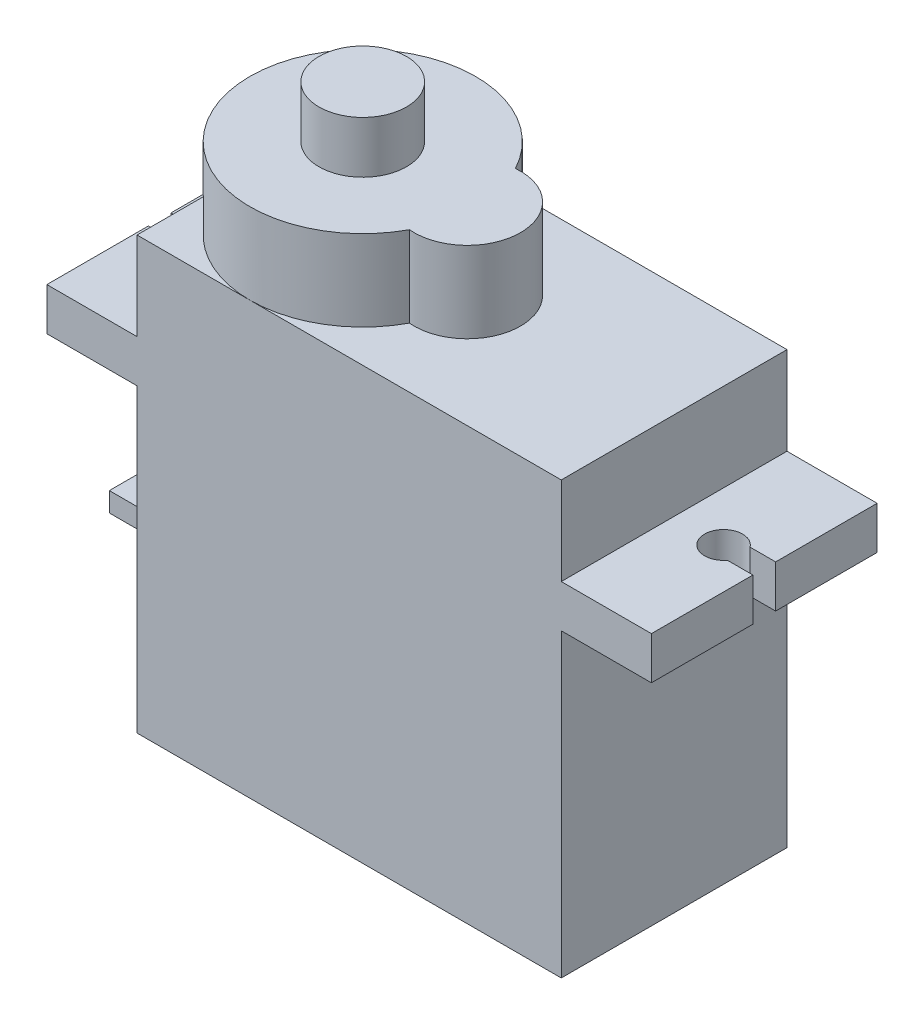
SolidWorks part; units mm, degrees
ref_plane "Front Plane" through (0, 0, 0) normal (0, 0, 1) x (1, 0, 0)
ref_plane "Top Plane" through (0, 0, 0) normal (0, 1, 0) x (1, 0, 0)
ref_plane "Right Plane" through (0, 0, 0) normal (1, 0, 0) x (0, 0, -1)
sketch "Sketch1" plane through (0, 0, 0) normal (0, 1, 0) x (1, 0, 0)
  line L1 (0, 0) -> (22.7711, 0)
  line L2 (0, 0) -> (0, 12.1158)
  line L3 (0, 12.1158) -> (22.7711, 12.1158)
  line L4 (22.7711, 0) -> (22.7711, 12.1158)
  dimension "D1" = 12.1158
  dimension "D2" = 22.7711
extrude "Boss-Extrude1" add sketch "Sketch1" along normal blind 23.1521
ref_plane "Plane1" through (0, 18.4277, 0) normal (0, 1, 0) x (1, 0, 0)
sketch "Sketch3" plane through (0, 18.4277, 0) normal (0, 1, 0) x (1, 0, 0)
  line L0 (22.7711, 12.1158) -> (0, 12.1158) construction
  line L1 (-4.8387, 0) -> (27.6098, 0)
  line L2 (-4.8387, 0) -> (-4.8387, 12.1158)
  line L3 (-4.8387, 12.1158) -> (27.6098, 12.1158)
  line L4 (27.6098, 0) -> (27.6098, 12.1158)
  line L5 (0, 0) -> (22.7711, 0) construction
  point P6 (11.3856, 0)
  point P9 (11.3856, 0)
  dimension "D1" = 32.4485
extrude "Boss-Extrude2" add sketch "Sketch3" against normal blind 2.286
sketch "Sketch4" plane through (0, 18.4277, 0) normal (0, 1, 0) x (1, 0, 0)
  line L0 (-3.4671, 6.6675) -> (-3.4671, 5.4483) construction
  line L1 (-4.8387, 6.6675) -> (-3.4671, 6.6675)
  line L2 (-4.8387, 12.1158) -> (-4.8387, 0) construction
  line L3 (-3.4671, 5.4483) -> (-4.8387, 5.4483)
  line L4 (-1.6383, 6.0579) -> (-1.6383, 8.3545) construction
  line L5 (11.3856, 12.1158) -> (11.3856, 0) construction
  line L6 (22.7711, 12.1158) -> (0, 12.1158) construction
  line L7 (0, 0) -> (22.7711, 0) construction
  line L8 (24.4094, 6.0579) -> (24.4094, 8.3545) construction
  line L9 (26.2382, 6.6675) -> (26.2382, 5.4483) construction
  line L10 (26.2382, 5.4483) -> (27.6098, 5.4483)
  line L11 (27.6098, 6.6675) -> (26.2382, 6.6675)
  line L12 (-4.8387, 6.6675) -> (-4.8387, 5.4483)
  line L13 (27.6098, 6.6675) -> (27.6098, 5.4483)
  arc A0 (-3.4671, 6.6675) -> (-3.4671, 5.4483) centre (-2.6543, 6.0579) cw
  arc A1 (26.2382, 6.6675) -> (26.2382, 5.4483) centre (25.4254, 6.0579) ccw
  point P6 (-3.4671, 6.0579)
  point P8 (-4.8387, 6.0579)
  dimension "D1" = 1.016
  dimension "D2" = 3.2004
  dimension "D3" = 1.2192
extrude "Cut-Extrude1" cut sketch "Sketch4" against normal through all
sketch "Sketch5" plane through (0, 23.1521, 0) normal (0, 1, 0) x (1, 0, 0)
  line L0 (22.7711, 12.1158) -> (0, 12.1158) construction
  line L1 (0, 12.1158) -> (0, 0) construction
  line L2 (0, 0) -> (22.7711, 0) construction
  line L3 (14.5288, 6.0579) -> (14.5288, 9.2952) construction
  arc A0 (11.4061, 8.9031) -> (11.4061, 3.2127) centre (6.0579, 6.0579) ccw
  arc A1 (11.4061, 3.2127) -> (11.4061, 8.9031) centre (11.6713, 6.0579) ccw
  dimension "D1" = 14.5288
  dimension "D2" = 5.715
extrude "Boss-Extrude3" add sketch "Sketch5" along normal blind 4.3434
sketch "Sketch6" plane through (0, 27.4955, 0) normal (0, 1, 0) x (1, 0, 0)
  circle A0 centre (6.0579, 6.0579) radius 2.3495
  arc A1 (11.4061, 8.9031) -> (11.4061, 3.2127) centre (6.0579, 6.0579) ccw construction
  dimension "D1" = 4.699
extrude "Boss-Extrude4" add sketch "Sketch6" along normal blind 2.7813 contours A0
sketch "Sketch7" plane through (0, 0, 0) normal (-1, 0, 0) x (0, 0, 1)
  line L0 (-12.1158, 0) -> (0, 0) construction
  line L1 (-7.5057, 4.8768) -> (-4.6101, 4.8768)
  line L2 (-7.5057, 4.8768) -> (-7.5057, 5.9182)
  line L3 (-7.5057, 5.9182) -> (-4.6101, 5.9182)
  line L4 (-4.6101, 4.8768) -> (-4.6101, 5.9182)
  point P4 (-6.0579, 4.8768)
  point P7 (-6.0579, 0)
  dimension "D1" = 1.0414
  dimension "D2" = 2.8956
  dimension "D3" = 4.8768
extrude "Boss-Extrude5" add sketch "Sketch7" along normal blind 6.096
ref_axis "Axis1" through (6.0579, 30.2768, -6.0579) along (0, -1, 0)
ref_plane "Plane2" through (6.0579, 0, 0) normal (-1, 0, 0) x (0, 0, 1)
sketch "Sketch8" plane through (0, 27.4955, 0) normal (0, 1, 0) x (1, 0, 0)
  circle A0 centre (6.0579, 6.0579) radius 3.556
  dimension "D1" = 7.112
extrude "Boss-Extrude6" [suppressed] add sketch "Sketch8" along normal blind 4.4577
sketch "Sketch9" [suppressed] plane through (0, 31.9532, 0) normal (0, 1, 0) x (1, 0, 0)
  line L0 (2.5019, 6.0579) -> (3.8735, 18.5674)
  line L1 (3.8735, 18.5674) -> (8.2423, 18.5674)
  line L2 (8.2423, 18.5674) -> (9.6139, 6.0579)
  line L3 (6.0579, 6.0579) -> (6.0579, 18.5674) construction
  line L4 (2.5019, 6.0579) -> (9.6139, 6.0579)
  line L5 (8.9281, 12.3127) -> (6.0579, 12.3127) construction
  line L6 (6.0579, 12.3127) -> (3.1877, 12.3127) construction
  circle A0 centre (6.0579, 6.0579) radius 3.556 construction
  point P10 (6.0579, 18.5674)
  point P18 (6.0579, 2.5019)
  dimension "D1" = 4.3688
  dimension "D2" = 16.0655
extrude "Boss-Extrude7" [suppressed] add sketch "Sketch9" against normal blind 1.651
sketch "Sketch11" [suppressed] plane through (0, 31.9532, 0) normal (0, 1, 0) x (1, 0, 0)
  circle A0 centre (6.0579, 6.0579) radius 2.4257
  arc A1 (2.5864, 6.8284) -> (9.5294, 6.8284) centre (6.0579, 6.0579) ccw construction
  dimension "D1" = 4.8514
extrude "Cut-Extrude2" [suppressed] cut sketch "Sketch11" against normal blind 2.54
sketch "Sketch12" [suppressed] plane through (0, 29.4132, 0) normal (0, 1, 0) x (1, 0, 0)
  circle A0 centre (6.0579, 6.0579) radius 1.2001
  dimension "D1" = 2.4003
extrude "Cut-Extrude3" [suppressed] cut sketch "Sketch12" against normal up to surface (1.9177 mm away) up to face at (6.0579, 27.4955, -3.7084)
